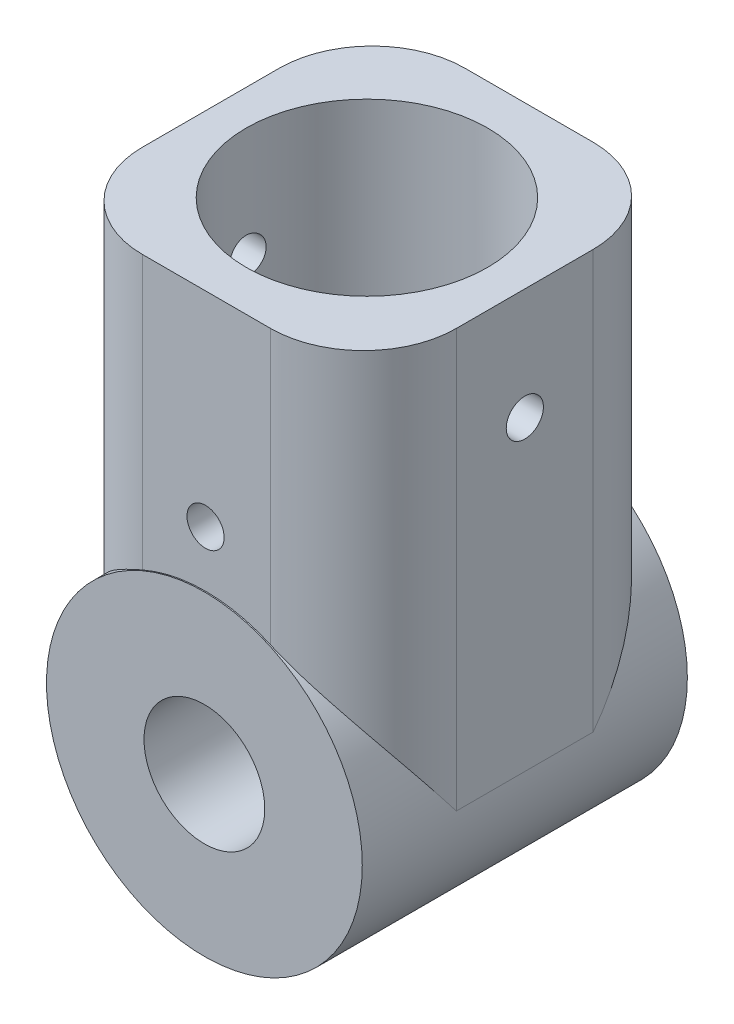
SolidWorks part; units mm, degrees
ref_plane "Спереди" through (0, 0, 0) normal (0, 0, 1) x (1, 0, 0)
ref_plane "Сверху" through (0, 0, 0) normal (0, 1, 0) x (1, 0, 0)
ref_plane "Справа" through (0, 0, 0) normal (1, 0, 0) x (0, 0, -1)
sketch "Эскиз1" plane through (0, 0, 0) normal (0, 0, 1) x (1, 0, 0)
  circle A0 centre (0, 0) radius 6.5
  circle A1 centre (0, 0) radius 17
extrude "Бобышка-Вытянуть2" add sketch "Эскиз1" along normal blind 35
ref_plane "Плоскость4" through (0, 45, 0) normal (0, 1, 0) x (1, 0, 0)
sketch "Эскиз3" plane through (0, 45, 0) normal (0, 1, 0) x (1, 0, 0)
  line L0 (17, -35) -> (17, 0) construction
  line L13 (-16.7953, -0.1471) -> (17, -0.1471)
  line L14 (-16.7953, -0.1471) -> (-16.7953, -34.8751)
  line L15 (-16.7953, -34.8751) -> (17, -34.8751)
  line L16 (17, -0.1471) -> (17, -34.8751)
  line L17 (-16.7953, -0.1471) -> (-17, 0) construction
  line L18 (-17, 0) -> (-17, -35) construction
  line L19 (-16.7953, -34.8751) -> (-17, -35) construction
  circle A1 centre (0, -17.5) radius 13
extrude "Бобышка-Вытянуть7" add sketch "Эскиз3" against normal blind 45
sketch "Эскиз4" plane through (0, 0, 0) normal (0, 0, -1) x (-1, 0, 0)
  circle A0 centre (0, 0) radius 6.5
extrude "Вырез-Вытянуть1" cut sketch "Эскиз4" against normal through all
sketch "Эскиз12" plane through (0, 0, 0) normal (0, 0, -1) x (-1, 0, 0)
  line L0 (0, 23) -> (0, 0) construction
  circle A3 centre (0, 23) radius 2
extrude "Вырез-Вытянуть11" cut sketch "Эскиз12" against normal blind 45
sketch "Эскиз15" plane through (-16.7953, 0, 0) normal (-1, 0, 0) x (0, 0, 1)
  line L0 (0, 0) -> (0, 33) construction
  line L1 (0, 33) -> (17.5, 33) construction
  circle A1 centre (17.5, 33) radius 2
extrude "Вырез-Вытянуть12" cut sketch "Эскиз15" against normal blind 45
fillet "Скругление4" radius 10 4 edges at (-16.7953, 23.8152, 0.1471) (17, 22.5, 0.1471) (17, 22.5, 34.8751) (-16.7953, 23.8152, 34.8751)
sketch "Эскиз20" plane through (0, 45, 0) normal (0, 1, 0) x (1, 0, 0)
  circle A3 centre (0, -17.5) radius 13
extrude "Вырез-Вытянуть18" cut sketch "Эскиз20" against normal blind 31
sketch "Эскиз25" plane through (0, 14, 0) normal (0, 1, 0) x (1, 0, 0)
  circle A2 centre (0, -17.5) radius 13
extrude "Бобышка-Вытянуть10" add sketch "Эскиз25" along normal blind 1
sketch3d "Трехмерный эскиз1"
  point P0 (-14.7779, 8.4033, 37.4657)
